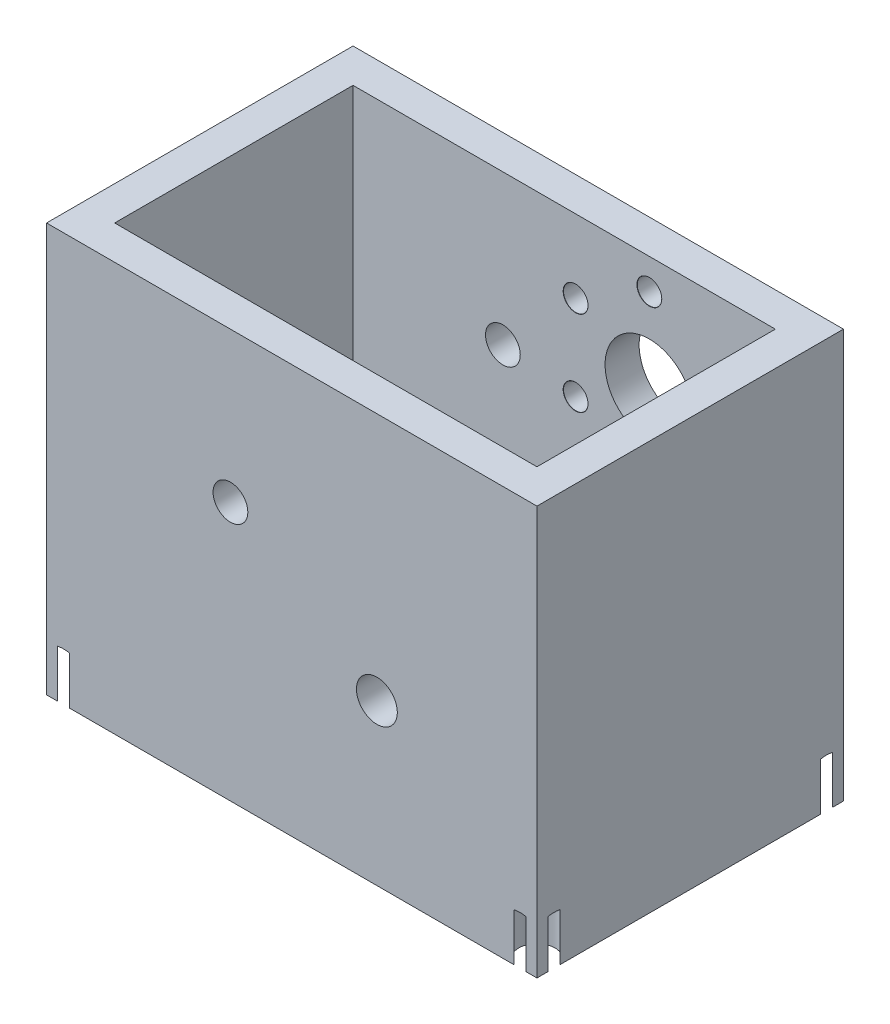
SolidWorks part; units mm, degrees
material "PLA"
ref_plane "Front Plane" through (0, 0, 0) normal (0, 0, 1) x (1, 0, 0)
ref_plane "Top Plane" through (0, 0, 0) normal (0, 1, 0) x (1, 0, 0)
ref_plane "Right Plane" through (0, 0, 0) normal (1, 0, 0) x (0, 0, -1)
sketch "Sketch1" plane through (0, 0, 0) normal (0, 1, 0) x (1, 0, 0)
  line L0 (-31, 0) -> (31, 0)
  line L1 (31, 0) -> (31, -27)
  line L2 (31, -27) -> (36, -27) construction
  line L3 (36, -27) -> (36, 5)
  line L4 (36, 5) -> (-36, 5)
  line L5 (-36, 5) -> (-36, -27)
  line L6 (-36, -27) -> (-31, -27) construction
  line L7 (-31, -27) -> (-31, 0)
  line L8 (-31, 0) -> (-36, 0)
  line L9 (31, 0) -> (36, 0)
  line L10 (-33.5, -37.5) -> (-33.5, 2.5) construction
  line L11 (-33.5, 2.5) -> (33.5, 2.5) construction
  line L12 (33.5, 2.5) -> (33.5, -37.5) construction
  line L13 (-36, -27) -> (-36, -40)
  line L14 (-36, -40) -> (36, -40)
  line L15 (36, -40) -> (36, -27)
  line L16 (31, -27) -> (31, -35)
  line L17 (31, -35) -> (-31, -35)
  line L18 (-31, -35) -> (-31, -27)
  line L19 (-33.5, -37.5) -> (33.7816, -37.5) construction
  point P8 (0, 0)
  point P12 (-33.5, -37.5)
  point P13 (33.5, -37.5)
  point P14 (33.5, 2.5)
  point P15 (-33.5, 2.5)
  dimension "D1" = 5
  dimension "D2" = 5
  dimension "D3" = 5
  dimension "D4" = 62
  dimension "D5" = 27
  dimension "D6" = 35
  dimension "D7" = 5
extrude "Boss-Extrude1" add sketch "Sketch1" along normal blind 60 contours L7 L8 L5 L6 | L0 L9 L3 L4 L5 L8 | L9 L1 L2 L3 region at (0, 0, -2.5) region at (-31.8237, 0, 13.5)
sketch "Sketch4" plane through (0, 0, 0) normal (0, 0, 1) x (1, 0, 0)
  line L1 (-31, 0) -> (31, 0) construction
  line L3 (12.5, 44) -> (12.5, 23.6384) construction
  line L6 (36, 60) -> (36, 0) construction
  circle A0 centre (12.5, 43) radius 12.5 construction
  circle A1 centre (12.5, 43) radius 6.5
  point P0 (12.5, 43)
  point P7 (12.5, 55.5)
  point P11 (23.3253, 49.25)
  point P12 (23.3253, 36.75)
  point P13 (12.5, 30.5)
  point P14 (1.6747, 36.75)
  point P15 (1.6747, 49.25)
  point P16 (12.5, 43)
  dimension "D3" = 25
  dimension "D5" = 13
  dimension "D1" = 23.5
  dimension "D2" = 43
  dimension "D4" = 6
hole_wizard "M3 Clearance Hole1" positions "Sketch5" profile "Sketch6" hole size "M3" standard "ISO" end condition through all
sketch "Sketch5" plane through (0, 0, 0) normal (0, 0, 1) x (1, 0, 0)
  point P0 (12.5, 55.5)
  point P3 (23.3253, 49.25)
  point P6 (23.3253, 36.75)
  point P9 (12.5, 30.5)
  point P12 (1.6747, 36.75)
  point P15 (1.6747, 49.25)
sketch "Sketch6" plane through (12.5, 55.5, 0) normal (1, 0, 0) x (0, -1, 0)
  line L0 (0, 0) -> (0, 5)
  line L1 (0, 5) -> (1.8, 5)
  line L2 (1.8, 5) -> (1.8, 0.025)
  line L3 (1.8, 0.025) -> (1.825, 0)
  line L5 (1.825, 0) -> (0, 0)
  line L6 (-1.8, 0.025) -> (-1.825, 0) construction
  line L11 (0, -6.35) -> (0, 107.95) construction
  dimension "Thru Hole Dia." = 3.6
  dimension "Thru Hole Depth" = 5
  dimension "Near C'Sink Dia." = 3.65
  dimension "Near C'Sink Angle" = 90
extrude "Cut-Extrude1" cut sketch "Sketch4" against normal through all
hole_wizard "Ø5.3 (5.3) Diameter Hole1" positions "Sketch7" profile "Sketch9" hole size "Ø5.3" standard "ISO"
sketch "Sketch7" plane through (0, 0, 0) normal (0, -1, 0) x (-1, 0, 0)
  point P0 (-33.5, 2.5)
  point P3 (-33.5, -37.5)
  point P6 (33.5, 2.5)
  point P9 (33.5, -37.5)
sketch "Sketch9" plane through (33.5, 0, -2.5) normal (1, 0, 0) x (0, 0, -1)
  line L0 (0, 0) -> (0, 8.5923)
  line L1 (0, 8.5923) -> (2.65, 7)
  line L2 (2.65, 7) -> (2.65, 0)
  line L5 (2.65, 0) -> (0, 0)
  line L10 (0, 8.5923) -> (-2.65, 7) construction
  line L11 (0, -6.35) -> (0, 107.95) construction
  dimension "Hole Dia." = 5.3
  dimension "Hole Depth" = 7
  dimension "Drill Angle" = 118
sketch "Sketch10" plane through (0, 0, 0) normal (0, 0, 1) x (1, 0, 0)
  line L0 (-31, 0) -> (31, 0) construction
  line L1 (36, 60) -> (36, 0) construction
  circle A0 centre (12.5, 23.5) radius 3
  dimension "D2" = 6
  dimension "D1" = 23.5
  dimension "D3" = 23.5
extrude "Cut-Extrude2" cut sketch "Sketch10" against normal through all both and the other way through all
sketch "Sketch11" plane through (0, 0, 0) normal (0, 0, 1) x (1, 0, 0)
  line L2 (-31, 60) -> (31, 60) construction
  line L4 (-36, 60) -> (-36, 0) construction
  circle A0 centre (-9, 38) radius 2.55
  dimension "D1" = 5.1
  dimension "D2" = 27
  dimension "D3" = 22
extrude "Cut-Extrude3" cut sketch "Sketch11" against normal through all both and the other way through all
